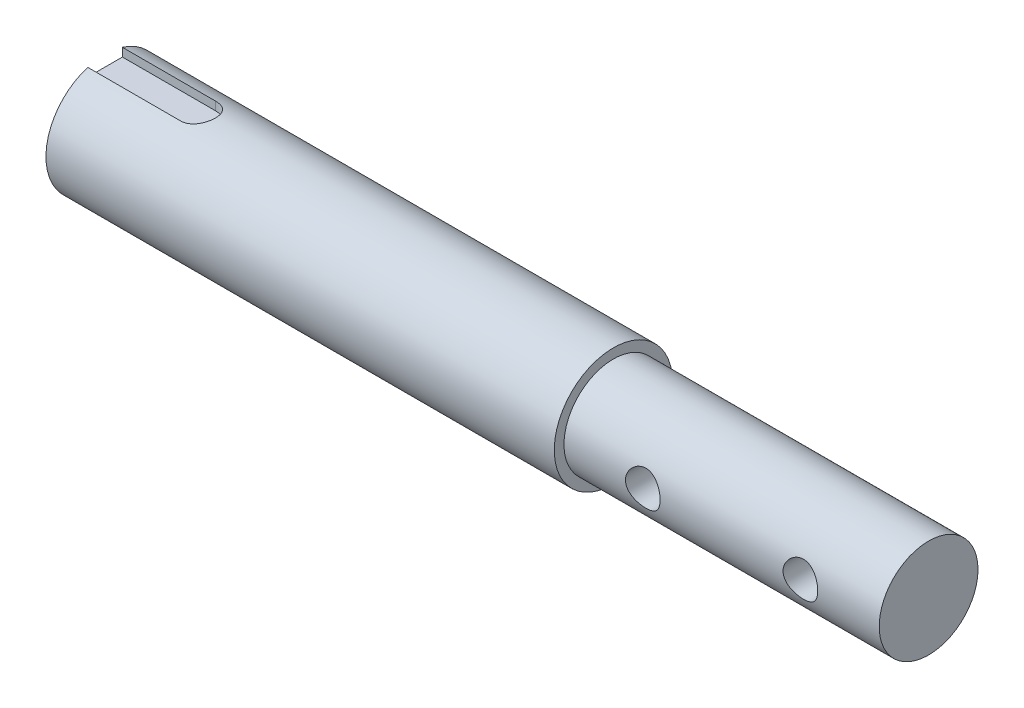
SolidWorks part; units mm, degrees
material "ASTM A36 Steel"
ref_plane "Front Plane" through (0, 0, 0) normal (0, 0, 1) x (1, 0, 0)
ref_plane "Top Plane" through (0, 0, 0) normal (0, 1, 0) x (1, 0, 0)
ref_plane "Right Plane" through (0, 0, 0) normal (1, 0, 0) x (0, 0, -1)
sketch "Sketch1" plane through (0, 0, 0) normal (1, 0, 0) x (0, 0, -1)
  circle A0 centre (0, 0) radius 37.5
  dimension "D1" = 75
extrude "Boss-Extrude1" add sketch "Sketch1" along normal blind 322.5
sketch "Sketch2" plane through (322.5, 0, 0) normal (1, 0, 0) x (0, 0, -1)
  circle A0 centre (0, 0) radius 31.34
  dimension "D1" = 62.68
extrude "Boss-Extrude2" add sketch "Sketch2" along normal blind 200
ref_plane "Plane1" through (0, 37.5, 0) normal (0, 1, 0) x (1, 0, 0)
sketch "Sketch3" plane through (0, 37.5, 0) normal (0, 1, 0) x (1, 0, 0)
  line L0 (0, 37.5) -> (0, -37.5) construction
  line L1 (59, -11) -> (0, -11)
  line L2 (0, -11) -> (0, 11)
  line L3 (0, 11) -> (59, 11)
  arc A0 (59, -11) -> (59, 11) centre (59, 0) ccw
  dimension "D1" = 22
  dimension "D2" = 59
extrude "Cut-Extrude1" cut sketch "Sketch3" against normal blind 7
sketch "Sketch4" plane through (0, 0, 0) normal (0, 0, 1) x (1, 0, 0)
  line L0 (322.5, -37.5) -> (322.5, 37.5) construction
  circle A0 centre (472.5, 0) radius 11
  circle A1 centre (372.5, 0) radius 11
  dimension "D1" = 22
  dimension "D2" = 50
  dimension "D3" = 22
  dimension "D4" = 100
extrude "Cut-Extrude2" cut sketch "Sketch4" against normal through all both and the other way through all
sketch "Sketch5" plane through (0, 0, 0) normal (-1, 0, 0) x (0, 0, 1)
  circle A0 centre (0, 0) radius 5
  dimension "D1" = 10
extrude "Cut-Extrude3" cut sketch "Sketch5" against normal blind 50
thread "Thread1" pitch 1.25 method cut profile "Thread Profile1" start angle 0, offset 0, length 47, pitch 1.25, diameter 10
ref_plane "Plane2" through (0, 0, -5) normal (0, -1, 0) x (0, 0, -1)
sketch "Thread Profile1" plane through (0, 0, -5) normal (0, -1, 0) x (0, 0, -1)
  line L0 (0, 0) -> (0, 1.25) construction
  line L1 (0, 0) -> (0.6766, 0.3906)
  line L2 (0.6766, 0.3906) -> (0.6766, 0.5469)
  line L3 (0.6766, 0.5469) -> (0, 0.9375)
  line L4 (0.6766, 0.4687) -> (0, 0.4687) construction
  line L11 (0, 0) -> (0, 0.9375)
  point P2 (0, 0)
  dimension "Pitch" = 1.25
  dimension "Profile_Angle" = 60
  dimension "Profile_Land" = 0.1562
  dimension "Profile_Height" = 0.6766
